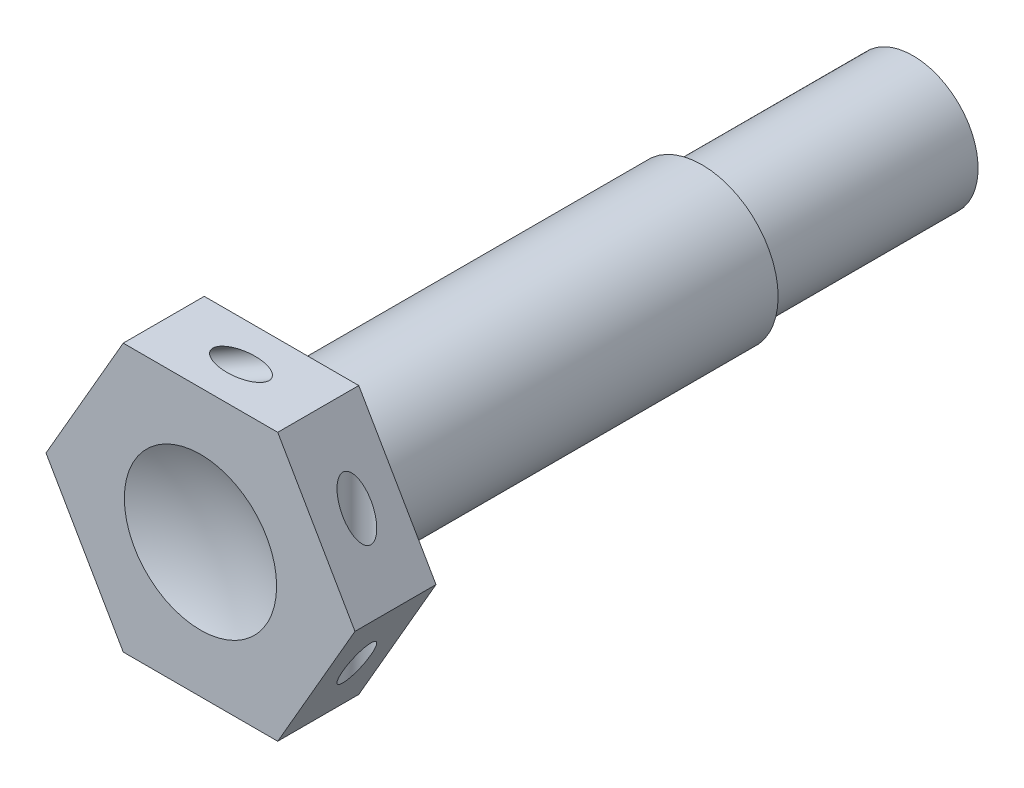
SolidWorks part; units mm, degrees
material "Alloy Steel"
ref_plane "Plane1" through (0, 0, 0) normal (0, 0, 1) x (1, 0, 0)
ref_plane "Plane2" through (0, 0, 0) normal (0, 1, 0) x (1, 0, 0)
ref_plane "Plane3" through (0, 0, 0) normal (1, 0, 0) x (0, 0, -1)
ref_axis "Axis1" through (-83.9706, 0, 0) along (1, 0, 0)
ref_axis "Axis2" through (0, 0, -27.705) along (0, 0, 1)
ref_axis "Axis3" through (0, 6.1119, 0) along (0, -1, 0)
sketch "Sketch1" plane through (0, 0, 0) normal (0, 0, 1) x (1, 0, 0)
  line L1 (3.2079, 5.5562) -> (-3.2079, 5.5562)
  line L2 (-3.2079, 5.5562) -> (-6.4158, 0)
  line L3 (-6.4158, 0) -> (-3.2079, -5.5563)
  line L4 (-3.2079, -5.5563) -> (3.2079, -5.5563)
  line L5 (3.2079, -5.5563) -> (6.4158, 0)
  line L6 (6.4158, 0) -> (3.2079, 5.5562)
  circle A0 centre (0, 0) radius 5.5562 construction
  dimension "D1" = 11.1125
extrude "Boss-Extrude1" add sketch "Sketch1" along normal blind 3.3655
sketch "Sketch2" plane through (0, 0, 0) normal (0, 0, -1) x (-1, 0, 0)
  circle A0 centre (0, 0) radius 3.1623
  dimension "D1" = 6.3246
extrude "Boss-Extrude2" add sketch "Sketch2" along normal blind 17.4625
sketch "Sketch3" plane through (0, 0, -17.4625) normal (0, 0, -1) x (-1, 0, 0)
  circle A0 centre (0, 0) radius 2.7051
  dimension "D1" = 5.4102
extrude "Boss-Extrude3" add sketch "Sketch3" along normal blind 8.763
sketch "Sketch4" plane through (0, 0, 0) normal (1, 0, 0) x (0, 0, -1)
  line L0 (-3.3655, 0) -> (-3.3655, 3.1623)
  line L1 (-3.3655, 0) -> (-3.3655, 5.5562) construction
  line L2 (-3.3655, 0) -> (0, 0) construction
  line L3 (-3.3655, 0) -> (-2.6644, 0)
  line L4 (-2.6644, 0) -> (-2.6644, 2.4426) construction
  line L5 (-3.3655, 3.1623) -> (-3.5111, 3.4745) construction
  arc A0 (-3.3655, 3.1623) -> (-2.6644, 0) centre (-10.1471, 0) cw
  dimension "D1" = 3.1623
  dimension "D2" = 25
revolve "Cut-Revolve1" cut sketch "Sketch4" angle 360 about L3
sketch "Sketch5" plane through (0, 0, 0) normal (0, 1, 0) x (1, 0, 0)
  line L0 (4.8119, -1.6827) -> (6.4158, -1.6827) construction
  line L1 (6.4158, -3.3655) -> (6.4158, 0) construction
  line L2 (4.8119, -1.6827) -> (3.2079, -1.6827) construction
  line L4 (3.2079, -3.3655) -> (3.2079, 0) construction
  circle A0 centre (4.8119, -1.6827) radius 0.5842
  dimension "D1" = 1.1684
extrude "Cut-Extrude1" cut sketch "Sketch5" against normal through all and the other way through all
pattern_circular "CirPattern1" count 3 over 360 about axis through (0, 0, -27.705) along (0, 0, 1) of "Cut-Extrude1"
equation "\"hexwid\"= 0.4375"
equation "\"hexht\"= 0.1325"
equation "\"gripd\"= 0.249"
equation "\"threadd\"= 0.213"
equation "\"threadlen\"= 0.37"
equation "\"wd\"= 0.046"
equation "\"griplen\"= 0.6875"
equation "\"D1@Sketch1\" = \"hexwid\""
equation "\"D1@Boss-Extrude1\" = \"hexht\""
equation "\"D1@Sketch2\" = \"gripd\""
equation "\"D1@Boss-Extrude2\" = \"griplen\""
equation "\"D1@Sketch3\" = \"threadd\""
equation "\"D1@Sketch4\" = \"gripd\"/2"
equation "\"D2@Sketch4\" = 25deg"
equation "\"D1@Cut-Revolve1\" = 360deg"
equation "\"D1@Sketch5\" = \"wd\""
equation "\"D3@CirPattern1\" = 360deg"
equation "\"D1@CirPattern1\" = 3"
